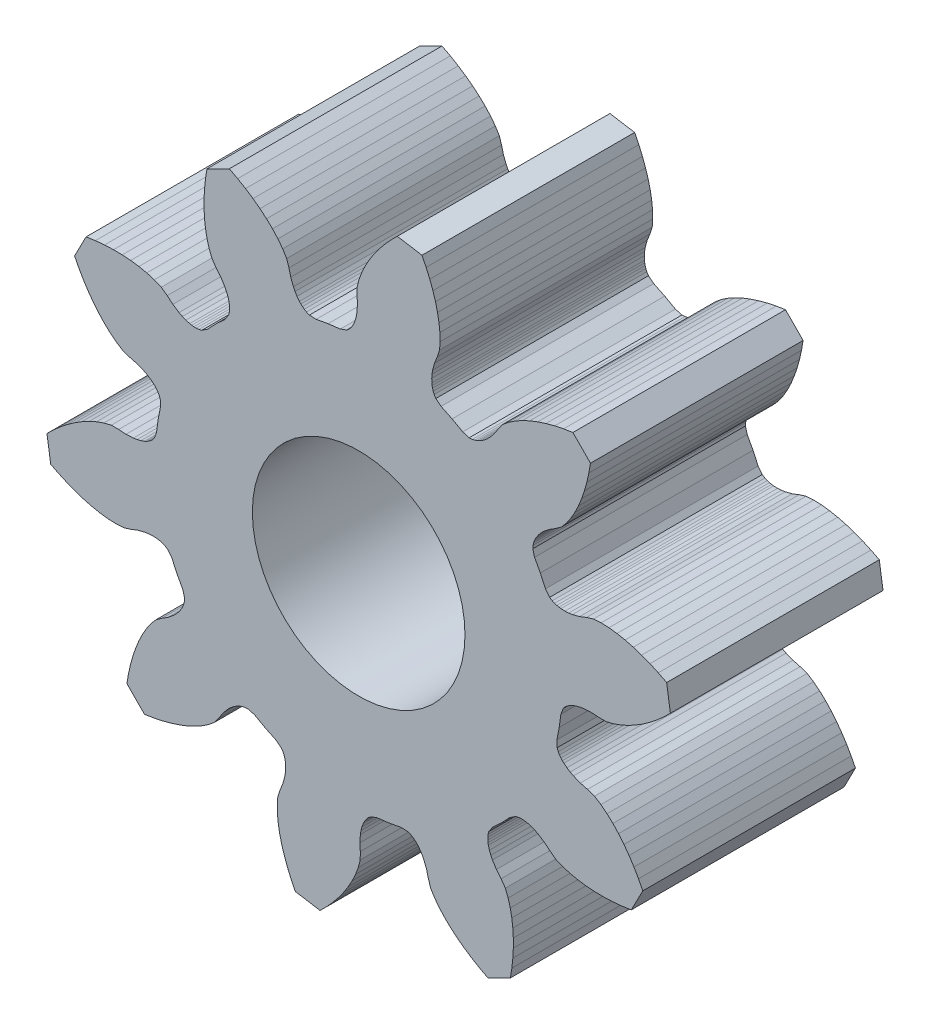
SolidWorks part; units mm, degrees
material "1060 Alloy"
ref_plane "Front Plane" through (0, 0, 0) normal (0, 0, 1) x (1, 0, 0)
ref_plane "Top Plane" through (0, 0, 0) normal (0, 1, 0) x (1, 0, 0)
ref_plane "Right Plane" through (0, 0, 0) normal (1, 0, 0) x (0, 0, -1)
sketch "Sketch1" plane through (0, 0, 0) normal (0, 0, 1) x (1, 0, 0)
  line L0 (-8.7858, -3.765) -> (-8.9815, -3.5156)
  line L1 (-8.9815, -3.5156) -> (-9.1044, -3.4371)
  line L2 (-9.1044, -3.4371) -> (-9.2148, -3.3885)
  line L3 (-9.2148, -3.3885) -> (-9.3186, -3.3562)
  line L4 (-9.3186, -3.3562) -> (-9.4181, -3.3349)
  line L5 (-9.4181, -3.3349) -> (-9.5145, -3.3217)
  line L6 (-9.5145, -3.3217) -> (-9.7003, -3.3138)
  line L7 (-9.7003, -3.3138) -> (-9.8793, -3.3247)
  line L8 (-9.8793, -3.3247) -> (-10.0533, -3.3502)
  line L9 (-10.0533, -3.3502) -> (-10.3894, -3.4364)
  line L10 (-10.3894, -3.4364) -> (-10.7128, -3.5607)
  line L11 (-10.7128, -3.5607) -> (-11.0431, -3.6644)
  line L12 (-11.0431, -3.6644) -> (-11.4, -3.6866)
  line L13 (-11.4, -3.6866) -> (-11.7679, -3.6716)
  line L14 (-11.7679, -3.6716) -> (-12.1438, -3.6256)
  line L15 (-12.1438, -3.6256) -> (-12.5259, -3.5514)
  line L16 (-12.5259, -3.5514) -> (-12.9126, -3.4504)
  line L17 (-12.9126, -3.4504) -> (-13.3028, -3.3238)
  line L18 (-13.3028, -3.3238) -> (-13.6953, -3.1723)
  line L19 (-13.6953, -3.1723) -> (-14.0889, -2.9962)
  line L20 (-14.0889, -2.9962) -> (-14.4827, -2.7961)
  line L21 (-14.4827, -2.7961) -> (-14.6595, -1.6321)
  line L22 (-14.6595, -1.6321) -> (-14.343, -1.324)
  line L23 (-14.343, -1.324) -> (-14.0194, -1.039)
  line L24 (-14.0194, -1.039) -> (-13.6897, -0.7777)
  line L25 (-13.6897, -0.7777) -> (-13.3547, -0.5409)
  line L26 (-13.3547, -0.5409) -> (-13.0154, -0.3297)
  line L27 (-13.0154, -0.3297) -> (-12.6726, -0.1453)
  line L28 (-12.6726, -0.1453) -> (-12.3273, 0.0103)
  line L29 (-12.3273, 0.0103) -> (-11.9805, 0.1339)
  line L30 (-11.9805, 0.1339) -> (-11.6331, 0.2187)
  line L31 (-11.6331, 0.2187) -> (-11.2869, 0.2178)
  line L32 (-11.2869, 0.2178) -> (-10.9412, 0.1951)
  line L33 (-10.9412, 0.1951) -> (-10.5947, 0.2127)
  line L34 (-10.5947, 0.2127) -> (-10.421, 0.24)
  line L35 (-10.421, 0.24) -> (-10.2468, 0.2828)
  line L36 (-10.2468, 0.2828) -> (-10.0717, 0.3455)
  line L37 (-10.0717, 0.3455) -> (-9.9836, 0.3867)
  line L38 (-9.9836, 0.3867) -> (-9.895, 0.4366)
  line L39 (-9.895, 0.4366) -> (-9.8054, 0.4983)
  line L40 (-9.8054, 0.4983) -> (-9.7144, 0.5775)
  line L41 (-9.7144, 0.5775) -> (-9.6204, 0.689)
  line L42 (-9.6204, 0.689) -> (-9.5076, 0.9853)
  line L43 (-9.5076, 0.9853) -> (-9.4312, 1.5547)
  line L44 (-9.4312, 1.5547) -> (-9.3208, 2.1184)
  line L45 (-9.3208, 2.1184) -> (-9.3325, 2.4352)
  line L46 (-9.3325, 2.4352) -> (-9.3858, 2.571)
  line L47 (-9.3858, 2.571) -> (-9.4466, 2.6752)
  line L48 (-9.4466, 2.6752) -> (-9.5116, 2.7624)
  line L49 (-9.5116, 2.7624) -> (-9.5796, 2.8381)
  line L50 (-9.5796, 2.8381) -> (-9.6498, 2.9054)
  line L51 (-9.6498, 2.9054) -> (-9.7955, 3.021)
  line L52 (-9.7955, 3.021) -> (-9.9467, 3.1175)
  line L53 (-9.9467, 3.1175) -> (-10.1024, 3.199)
  line L54 (-10.1024, 3.199) -> (-10.425, 3.3269)
  line L55 (-10.425, 3.3269) -> (-10.7597, 3.4164)
  line L56 (-10.7597, 3.4164) -> (-11.0878, 3.5266)
  line L57 (-11.0878, 3.5266) -> (-11.3896, 3.7184)
  line L58 (-11.3896, 3.7184) -> (-11.6785, 3.9468)
  line L59 (-11.6785, 3.9468) -> (-11.9556, 4.205)
  line L60 (-11.9556, 4.205) -> (-12.221, 4.4896)
  line L61 (-12.221, 4.4896) -> (-12.4746, 4.7986)
  line L62 (-12.4746, 4.7986) -> (-12.7159, 5.1304)
  line L63 (-12.7159, 5.1304) -> (-12.9443, 5.4837)
  line L64 (-12.9443, 5.4837) -> (-13.1593, 5.8575)
  line L65 (-13.1593, 5.8575) -> (-13.3602, 6.2508)
  line L66 (-13.3602, 6.2508) -> (-12.8191, 7.2965)
  line L67 (-12.8191, 7.2965) -> (-12.3819, 7.3597)
  line L68 (-12.3819, 7.3597) -> (-11.9526, 7.4001)
  line L69 (-11.9526, 7.4001) -> (-11.5323, 7.4176)
  line L70 (-11.5323, 7.4176) -> (-11.1221, 7.4123)
  line L71 (-11.1221, 7.4123) -> (-10.7234, 7.3838)
  line L72 (-10.7234, 7.3838) -> (-10.3377, 7.3315)
  line L73 (-10.3377, 7.3315) -> (-9.9669, 7.2544)
  line L74 (-9.9669, 7.2544) -> (-9.6137, 7.1505)
  line L75 (-9.6137, 7.1505) -> (-9.2828, 7.0149)
  line L76 (-9.2828, 7.0149) -> (-9.0033, 6.8107)
  line L77 (-9.0033, 6.8107) -> (-8.7368, 6.5892)
  line L78 (-8.7368, 6.5892) -> (-8.4462, 6.3997)
  line L79 (-8.4462, 6.3997) -> (-8.2897, 6.3197)
  line L80 (-8.2897, 6.3197) -> (-8.1236, 6.2519)
  line L81 (-8.1236, 6.2519) -> (-7.945, 6.1998)
  line L82 (-7.945, 6.1998) -> (-7.8496, 6.1813)
  line L83 (-7.8496, 6.1813) -> (-7.7485, 6.1696)
  line L84 (-7.7485, 6.1696) -> (-7.6398, 6.1668)
  line L85 (-7.6398, 6.1668) -> (-7.5196, 6.1774)
  line L86 (-7.5196, 6.1774) -> (-7.378, 6.2124)
  line L87 (-7.378, 6.2124) -> (-7.1126, 6.3858)
  line L88 (-7.1126, 6.3858) -> (-6.7162, 6.8015)
  line L89 (-6.7162, 6.8015) -> (-6.2955, 7.1927)
  line L90 (-6.2955, 7.1927) -> (-6.1188, 7.4559)
  line L91 (-6.1188, 7.4559) -> (-6.082, 7.597)
  line L92 (-6.082, 7.597) -> (-6.07, 7.7171)
  line L93 (-6.07, 7.7171) -> (-6.0713, 7.8258)
  line L94 (-6.0713, 7.8258) -> (-6.0818, 7.927)
  line L95 (-6.0818, 7.927) -> (-6.099, 8.0227)
  line L96 (-6.099, 8.0227) -> (-6.1489, 8.2019)
  line L97 (-6.1489, 8.2019) -> (-6.2146, 8.3688)
  line L98 (-6.2146, 8.3688) -> (-6.2927, 8.5263)
  line L99 (-6.2927, 8.5263) -> (-6.4784, 8.8194)
  line L100 (-6.4784, 8.8194) -> (-6.6966, 9.0885)
  line L101 (-6.6966, 9.0885) -> (-6.8973, 9.3706)
  line L102 (-6.8973, 9.3706) -> (-7.0287, 9.7032)
  line L103 (-7.0287, 9.7032) -> (-7.1282, 10.0577)
  line L104 (-7.1282, 10.0577) -> (-7.2006, 10.4294)
  line L105 (-7.2006, 10.4294) -> (-7.248, 10.8157)
  line L106 (-7.248, 10.8157) -> (-7.2715, 11.2148)
  line L107 (-7.2715, 11.2148) -> (-7.2717, 11.625)
  line L108 (-7.2717, 11.625) -> (-7.2489, 12.0451)
  line L109 (-7.2489, 12.0451) -> (-7.2031, 12.4739)
  line L110 (-7.2031, 12.4739) -> (-7.1344, 12.9102)
  line L111 (-7.1344, 12.9102) -> (-6.0821, 13.4381)
  line L112 (-6.0821, 13.4381) -> (-5.6913, 13.2322)
  line L113 (-5.6913, 13.2322) -> (-5.3202, 13.0126)
  line L114 (-5.3202, 13.0126) -> (-4.9698, 12.7797)
  line L115 (-4.9698, 12.7797) -> (-4.6411, 12.5343)
  line L116 (-4.6411, 12.5343) -> (-4.3353, 12.2769)
  line L117 (-4.3353, 12.2769) -> (-4.054, 12.0079)
  line L118 (-4.054, 12.0079) -> (-3.7993, 11.7276)
  line L119 (-3.7993, 11.7276) -> (-3.5746, 11.4359)
  line L120 (-3.5746, 11.4359) -> (-3.3866, 11.1317)
  line L121 (-3.3866, 11.1317) -> (-3.2805, 10.8022)
  line L122 (-3.2805, 10.8022) -> (-3.1952, 10.4664)
  line L123 (-3.1952, 10.4664) -> (-3.0714, 10.1422)
  line L124 (-3.0714, 10.1422) -> (-2.9918, 9.9855)
  line L125 (-2.9918, 9.9855) -> (-2.8973, 9.833)
  line L126 (-2.8973, 9.833) -> (-2.7835, 9.6859)
  line L127 (-2.7835, 9.6859) -> (-2.7171, 9.6149)
  line L128 (-2.7171, 9.6149) -> (-2.6422, 9.546)
  line L129 (-2.6422, 9.546) -> (-2.5559, 9.4799)
  line L130 (-2.5559, 9.4799) -> (-2.4524, 9.4178)
  line L131 (-2.4524, 9.4178) -> (-2.3173, 9.3628)
  line L132 (-2.3173, 9.3628) -> (-2.0007, 9.3471)
  line L133 (-2.0007, 9.3471) -> (-1.4356, 9.4504)
  line L134 (-1.4356, 9.4504) -> (-0.8654, 9.5196)
  line L135 (-0.8654, 9.5196) -> (-0.5677, 9.6287)
  line L136 (-0.5677, 9.6287) -> (-0.455, 9.7213)
  line L137 (-0.455, 9.7213) -> (-0.3747, 9.8113)
  line L138 (-0.3747, 9.8113) -> (-0.3119, 9.9001)
  line L139 (-0.3119, 9.9001) -> (-0.2608, 9.9881)
  line L140 (-0.2608, 9.9881) -> (-0.2185, 10.0757)
  line L141 (-0.2185, 10.0757) -> (-0.1536, 10.2499)
  line L142 (-0.1536, 10.2499) -> (-0.1086, 10.4236)
  line L143 (-0.1086, 10.4236) -> (-0.0792, 10.5969)
  line L144 (-0.0792, 10.5969) -> (-0.0572, 10.9432)
  line L145 (-0.0572, 10.9432) -> (-0.0755, 11.2892)
  line L146 (-0.0755, 11.2892) -> (-0.0721, 11.6353)
  line L147 (-0.0721, 11.6353) -> (0.0171, 11.9816)
  line L148 (0.0171, 11.9816) -> (0.145, 12.3269)
  line L149 (0.145, 12.3269) -> (0.3049, 12.6702)
  line L150 (0.3049, 12.6702) -> (0.4936, 13.0106)
  line L151 (0.4936, 13.0106) -> (0.7091, 13.3473)
  line L152 (0.7091, 13.3473) -> (0.9501, 13.6793)
  line L153 (0.9501, 13.6793) -> (1.2155, 14.0057)
  line L154 (1.2155, 14.0057) -> (1.5046, 14.3256)
  line L155 (1.5046, 14.3256) -> (1.8166, 14.6383)
  line L156 (1.8166, 14.6383) -> (2.9783, 14.4468)
  line L157 (2.9783, 14.4468) -> (3.1734, 14.0506)
  line L158 (3.1734, 14.0506) -> (3.3445, 13.6548)
  line L159 (3.3445, 13.6548) -> (3.4911, 13.2604)
  line L160 (3.4911, 13.2604) -> (3.6128, 12.8687)
  line L161 (3.6128, 12.8687) -> (3.7089, 12.4806)
  line L162 (3.7089, 12.4806) -> (3.7783, 12.0977)
  line L163 (3.7783, 12.0977) -> (3.8196, 11.7212)
  line L164 (3.8196, 11.7212) -> (3.83, 11.3531)
  line L165 (3.83, 11.3531) -> (3.8032, 10.9965)
  line L166 (3.8032, 10.9965) -> (3.6954, 10.6676)
  line L167 (3.6954, 10.6676) -> (3.567, 10.3458)
  line L168 (3.567, 10.3458) -> (3.4767, 10.0108)
  line L169 (3.4767, 10.0108) -> (3.4489, 9.8372)
  line L170 (3.4489, 9.8372) -> (3.4358, 9.6583)
  line L171 (3.4358, 9.6583) -> (3.4414, 9.4724)
  line L172 (3.4414, 9.4724) -> (3.4534, 9.3759)
  line L173 (3.4534, 9.3759) -> (3.4734, 9.2761)
  line L174 (3.4734, 9.2761) -> (3.5044, 9.1719)
  line L175 (3.5044, 9.1719) -> (3.5516, 9.0609)
  line L176 (3.5516, 9.0609) -> (3.6286, 8.937)
  line L177 (3.6286, 8.937) -> (3.8755, 8.7381)
  line L178 (3.8755, 8.7381) -> (4.3934, 8.4896)
  line L179 (4.3934, 8.4896) -> (4.8954, 8.2104)
  line L180 (4.8954, 8.2104) -> (5.2004, 8.1237)
  line L181 (5.2004, 8.1237) -> (5.346, 8.1323)
  line L182 (5.346, 8.1323) -> (5.4639, 8.1579)
  line L183 (5.4639, 8.1579) -> (5.5669, 8.1929)
  line L184 (5.5669, 8.1929) -> (5.6599, 8.2341)
  line L185 (5.6599, 8.2341) -> (5.7456, 8.2801)
  line L186 (5.7456, 8.2801) -> (5.9005, 8.3829)
  line L187 (5.9005, 8.3829) -> (6.039, 8.4969)
  line L188 (6.039, 8.4969) -> (6.1647, 8.6198)
  line L189 (6.1647, 8.6198) -> (6.386, 8.8871)
  line L190 (6.386, 8.8871) -> (6.5746, 9.1777)
  line L191 (6.5746, 9.1777) -> (6.7808, 9.4557)
  line L192 (6.7808, 9.4557) -> (7.0565, 9.6835)
  line L193 (7.0565, 9.6835) -> (7.3629, 9.8877)
  line L194 (7.3629, 9.8877) -> (7.6941, 10.0714)
  line L195 (7.6941, 10.0714) -> (8.0468, 10.2359)
  line L196 (8.0468, 10.2359) -> (8.4191, 10.3816)
  line L197 (8.4191, 10.3816) -> (8.8092, 10.5085)
  line L198 (8.8092, 10.5085) -> (9.2158, 10.6166)
  line L199 (9.2158, 10.6166) -> (9.6377, 10.7055)
  line L200 (9.6377, 10.7055) -> (10.0739, 10.7751)
  line L201 (10.0739, 10.7751) -> (10.9011, 9.9373)
  line L202 (10.9011, 9.9373) -> (10.8261, 9.5021)
  line L203 (10.8261, 9.5021) -> (10.7319, 9.0813)
  line L204 (10.7319, 9.0813) -> (10.6187, 8.6761)
  line L205 (10.6187, 8.6761) -> (10.4869, 8.2876)
  line L206 (10.4869, 8.2876) -> (10.3365, 7.9173)
  line L207 (10.3365, 7.9173) -> (10.1676, 7.5666)
  line L208 (10.1676, 7.5666) -> (9.9797, 7.2377)
  line L209 (9.9797, 7.2377) -> (9.7718, 6.9339)
  line L210 (9.7718, 6.9339) -> (9.5405, 6.6611)
  line L211 (9.5405, 6.6611) -> (9.26, 6.4584)
  line L212 (9.26, 6.4584) -> (8.9669, 6.2735)
  line L213 (8.9669, 6.2735) -> (8.6969, 6.0556)
  line L214 (8.6969, 6.0556) -> (8.5725, 5.9314)
  line L215 (8.5725, 5.9314) -> (8.4567, 5.7944)
  line L216 (8.4567, 5.7944) -> (8.3519, 5.6407)
  line L217 (8.3519, 5.6407) -> (8.3049, 5.5556)
  line L218 (8.3049, 5.5556) -> (8.2625, 5.4631)
  line L219 (8.2625, 5.4631) -> (8.2263, 5.3606)
  line L220 (8.2263, 5.3606) -> (8.1992, 5.243)
  line L221 (8.1992, 5.243) -> (8.1887, 5.0975)
  line L222 (8.1887, 5.0975) -> (8.2716, 4.7916)
  line L223 (8.2716, 4.7916) -> (8.5445, 4.2861)
  line L224 (8.5445, 4.2861) -> (8.7865, 3.7651)
  line L225 (8.7865, 3.7651) -> (8.9822, 3.5157)
  line L226 (8.9822, 3.5157) -> (9.1051, 3.4371)
  line L227 (9.1051, 3.4371) -> (9.2155, 3.3885)
  line L228 (9.2155, 3.3885) -> (9.3194, 3.3563)
  line L229 (9.3194, 3.3563) -> (9.4189, 3.3349)
  line L230 (9.4189, 3.3349) -> (9.5152, 3.3218)
  line L231 (9.5152, 3.3218) -> (9.701, 3.3139)
  line L232 (9.701, 3.3139) -> (9.8801, 3.3247)
  line L233 (9.8801, 3.3247) -> (10.054, 3.3503)
  line L234 (10.054, 3.3503) -> (10.3901, 3.4364)
  line L235 (10.3901, 3.4364) -> (10.7135, 3.5607)
  line L236 (10.7135, 3.5607) -> (11.0438, 3.6644)
  line L237 (11.0438, 3.6644) -> (11.4007, 3.6867)
  line L238 (11.4007, 3.6867) -> (11.7686, 3.6717)
  line L239 (11.7686, 3.6717) -> (12.1445, 3.6257)
  line L240 (12.1445, 3.6257) -> (12.5266, 3.5514)
  line L241 (12.5266, 3.5514) -> (12.9134, 3.4505)
  line L242 (12.9134, 3.4505) -> (13.3036, 3.3239)
  line L243 (13.3036, 3.3239) -> (13.696, 3.1723)
  line L244 (13.696, 3.1723) -> (14.0897, 2.9963)
  line L245 (14.0897, 2.9963) -> (14.4834, 2.7962)
  line L246 (14.4834, 2.7962) -> (14.6603, 1.6322)
  line L247 (14.6603, 1.6322) -> (14.3438, 1.3241)
  line L248 (14.3438, 1.3241) -> (14.0202, 1.0391)
  line L249 (14.0202, 1.0391) -> (13.6904, 0.7778)
  line L250 (13.6904, 0.7778) -> (13.3555, 0.541)
  line L251 (13.3555, 0.541) -> (13.0161, 0.3297)
  line L252 (13.0161, 0.3297) -> (12.6734, 0.1453)
  line L253 (12.6734, 0.1453) -> (12.3281, -0.0103)
  line L254 (12.3281, -0.0103) -> (11.9812, -0.1338)
  line L255 (11.9812, -0.1338) -> (11.6338, -0.2186)
  line L256 (11.6338, -0.2186) -> (11.2877, -0.2177)
  line L257 (11.2877, -0.2177) -> (10.9419, -0.1951)
  line L258 (10.9419, -0.1951) -> (10.5954, -0.2126)
  line L259 (10.5954, -0.2126) -> (10.4217, -0.2399)
  line L260 (10.4217, -0.2399) -> (10.2475, -0.2827)
  line L261 (10.2475, -0.2827) -> (10.0725, -0.3455)
  line L262 (10.0725, -0.3455) -> (9.9844, -0.3867)
  line L263 (9.9844, -0.3867) -> (9.8957, -0.4366)
  line L264 (9.8957, -0.4366) -> (9.8061, -0.4982)
  line L265 (9.8061, -0.4982) -> (9.7151, -0.5774)
  line L266 (9.7151, -0.5774) -> (9.6211, -0.689)
  line L267 (9.6211, -0.689) -> (9.5083, -0.9852)
  line L268 (9.5083, -0.9852) -> (9.4319, -1.5546)
  line L269 (9.4319, -1.5546) -> (9.3215, -2.1183)
  line L270 (9.3215, -2.1183) -> (9.3333, -2.4351)
  line L271 (9.3333, -2.4351) -> (9.3865, -2.5709)
  line L272 (9.3865, -2.5709) -> (9.4473, -2.6751)
  line L273 (9.4473, -2.6751) -> (9.5123, -2.7623)
  line L274 (9.5123, -2.7623) -> (9.5803, -2.838)
  line L275 (9.5803, -2.838) -> (9.6505, -2.9053)
  line L276 (9.6505, -2.9053) -> (9.7962, -3.0209)
  line L277 (9.7962, -3.0209) -> (9.9474, -3.1174)
  line L278 (9.9474, -3.1174) -> (10.1032, -3.199)
  line L279 (10.1032, -3.199) -> (10.4257, -3.3268)
  line L280 (10.4257, -3.3268) -> (10.7604, -3.4163)
  line L281 (10.7604, -3.4163) -> (11.0886, -3.5266)
  line L282 (11.0886, -3.5266) -> (11.3904, -3.7184)
  line L283 (11.3904, -3.7184) -> (11.6792, -3.9467)
  line L284 (11.6792, -3.9467) -> (11.9563, -4.2049)
  line L285 (11.9563, -4.2049) -> (12.2217, -4.4896)
  line L286 (12.2217, -4.4896) -> (12.4753, -4.7986)
  line L287 (12.4753, -4.7986) -> (12.7166, -5.1303)
  line L288 (12.7166, -5.1303) -> (12.945, -5.4836)
  line L289 (12.945, -5.4836) -> (13.16, -5.8574)
  line L290 (13.16, -5.8574) -> (13.3609, -6.2508)
  line L291 (13.3609, -6.2508) -> (12.8198, -7.2964)
  line L292 (12.8198, -7.2964) -> (12.3827, -7.3596)
  line L293 (12.3827, -7.3596) -> (11.9534, -7.4)
  line L294 (11.9534, -7.4) -> (11.533, -7.4176)
  line L295 (11.533, -7.4176) -> (11.1228, -7.4122)
  line L296 (11.1228, -7.4122) -> (10.7241, -7.3837)
  line L297 (10.7241, -7.3837) -> (10.3384, -7.3314)
  line L298 (10.3384, -7.3314) -> (9.9676, -7.2543)
  line L299 (9.9676, -7.2543) -> (9.6144, -7.1504)
  line L300 (9.6144, -7.1504) -> (9.2835, -7.0148)
  line L301 (9.2835, -7.0148) -> (9.004, -6.8106)
  line L302 (9.004, -6.8106) -> (8.7376, -6.5891)
  line L303 (8.7376, -6.5891) -> (8.4469, -6.3996)
  line L304 (8.4469, -6.3996) -> (8.2904, -6.3196)
  line L305 (8.2904, -6.3196) -> (8.1243, -6.2519)
  line L306 (8.1243, -6.2519) -> (7.9458, -6.1997)
  line L307 (7.9458, -6.1997) -> (7.8503, -6.1812)
  line L308 (7.8503, -6.1812) -> (7.7492, -6.1695)
  line L309 (7.7492, -6.1695) -> (7.6405, -6.1668)
  line L310 (7.6405, -6.1668) -> (7.5203, -6.1773)
  line L311 (7.5203, -6.1773) -> (7.3787, -6.2123)
  line L312 (7.3787, -6.2123) -> (7.1133, -6.3857)
  line L313 (7.1133, -6.3857) -> (6.7169, -6.8014)
  line L314 (6.7169, -6.8014) -> (6.2962, -7.1926)
  line L315 (6.2962, -7.1926) -> (6.1195, -7.4558)
  line L316 (6.1195, -7.4558) -> (6.0828, -7.597)
  line L317 (6.0828, -7.597) -> (6.0707, -7.717)
  line L318 (6.0707, -7.717) -> (6.0721, -7.8257)
  line L319 (6.0721, -7.8257) -> (6.0825, -7.927)
  line L320 (6.0825, -7.927) -> (6.0998, -8.0227)
  line L321 (6.0998, -8.0227) -> (6.1497, -8.2018)
  line L322 (6.1497, -8.2018) -> (6.2153, -8.3687)
  line L323 (6.2153, -8.3687) -> (6.2934, -8.5263)
  line L324 (6.2934, -8.5263) -> (6.4792, -8.8193)
  line L325 (6.4792, -8.8193) -> (6.6973, -9.0885)
  line L326 (6.6973, -9.0885) -> (6.898, -9.3705)
  line L327 (6.898, -9.3705) -> (7.0294, -9.7031)
  line L328 (7.0294, -9.7031) -> (7.1289, -10.0576)
  line L329 (7.1289, -10.0576) -> (7.2013, -10.4293)
  line L330 (7.2013, -10.4293) -> (7.2488, -10.8157)
  line L331 (7.2488, -10.8157) -> (7.2723, -11.2147)
  line L332 (7.2723, -11.2147) -> (7.2725, -11.6249)
  line L333 (7.2725, -11.6249) -> (7.2496, -12.045)
  line L334 (7.2496, -12.045) -> (7.2038, -12.4738)
  line L335 (7.2038, -12.4738) -> (7.1351, -12.9101)
  line L336 (7.1351, -12.9101) -> (6.0828, -13.438)
  line L337 (6.0828, -13.438) -> (5.692, -13.2322)
  line L338 (5.692, -13.2322) -> (5.3209, -13.0125)
  line L339 (5.3209, -13.0125) -> (4.9705, -12.7797)
  line L340 (4.9705, -12.7797) -> (4.6418, -12.5342)
  line L341 (4.6418, -12.5342) -> (4.336, -12.2768)
  line L342 (4.336, -12.2768) -> (4.0547, -12.0078)
  line L343 (4.0547, -12.0078) -> (3.8, -11.7275)
  line L344 (3.8, -11.7275) -> (3.5754, -11.4358)
  line L345 (3.5754, -11.4358) -> (3.3874, -11.1316)
  line L346 (3.3874, -11.1316) -> (3.2812, -10.8021)
  line L347 (3.2812, -10.8021) -> (3.1959, -10.4663)
  line L348 (3.1959, -10.4663) -> (3.0722, -10.1422)
  line L349 (3.0722, -10.1422) -> (2.9925, -9.9854)
  line L350 (2.9925, -9.9854) -> (2.898, -9.833)
  line L351 (2.898, -9.833) -> (2.7842, -9.6859)
  line L352 (2.7842, -9.6859) -> (2.7178, -9.6148)
  line L353 (2.7178, -9.6148) -> (2.6429, -9.5459)
  line L354 (2.6429, -9.5459) -> (2.5566, -9.4798)
  line L355 (2.5566, -9.4798) -> (2.4532, -9.4177)
  line L356 (2.4532, -9.4177) -> (2.3181, -9.3627)
  line L357 (2.3181, -9.3627) -> (2.0014, -9.347)
  line L358 (2.0014, -9.347) -> (1.4363, -9.4503)
  line L359 (1.4363, -9.4503) -> (0.8661, -9.5195)
  line L360 (0.8661, -9.5195) -> (0.5684, -9.6286)
  line L361 (0.5684, -9.6286) -> (0.4557, -9.7212)
  line L362 (0.4557, -9.7212) -> (0.3754, -9.8112)
  line L363 (0.3754, -9.8112) -> (0.3126, -9.9)
  line L364 (0.3126, -9.9) -> (0.2616, -9.988)
  line L365 (0.2616, -9.988) -> (0.2193, -10.0756)
  line L366 (0.2193, -10.0756) -> (0.1543, -10.2499)
  line L367 (0.1543, -10.2499) -> (0.1093, -10.4235)
  line L368 (0.1093, -10.4235) -> (0.0799, -10.5968)
  line L369 (0.0799, -10.5968) -> (0.058, -10.9431)
  line L370 (0.058, -10.9431) -> (0.0762, -11.2891)
  line L371 (0.0762, -11.2891) -> (0.0728, -11.6352)
  line L372 (0.0728, -11.6352) -> (-0.0163, -11.9816)
  line L373 (-0.0163, -11.9816) -> (-0.1442, -12.3268)
  line L374 (-0.1442, -12.3268) -> (-0.3042, -12.6701)
  line L375 (-0.3042, -12.6701) -> (-0.4929, -13.0106)
  line L376 (-0.4929, -13.0106) -> (-0.7084, -13.3472)
  line L377 (-0.7084, -13.3472) -> (-0.9494, -13.6792)
  line L378 (-0.9494, -13.6792) -> (-1.2148, -14.0056)
  line L379 (-1.2148, -14.0056) -> (-1.5038, -14.3256)
  line L380 (-1.5038, -14.3256) -> (-1.8159, -14.6382)
  line L381 (-1.8159, -14.6382) -> (-2.9775, -14.4467)
  line L382 (-2.9775, -14.4467) -> (-3.1727, -14.0505)
  line L383 (-3.1727, -14.0505) -> (-3.3438, -13.6547)
  line L384 (-3.3438, -13.6547) -> (-3.4904, -13.2603)
  line L385 (-3.4904, -13.2603) -> (-3.6121, -12.8686)
  line L386 (-3.6121, -12.8686) -> (-3.7081, -12.4806)
  line L387 (-3.7081, -12.4806) -> (-3.7776, -12.0976)
  line L388 (-3.7776, -12.0976) -> (-3.8189, -11.7211)
  line L389 (-3.8189, -11.7211) -> (-3.8292, -11.3531)
  line L390 (-3.8292, -11.3531) -> (-3.8025, -10.9965)
  line L391 (-3.8025, -10.9965) -> (-3.6947, -10.6675)
  line L392 (-3.6947, -10.6675) -> (-3.5663, -10.3457)
  line L393 (-3.5663, -10.3457) -> (-3.4759, -10.0107)
  line L394 (-3.4759, -10.0107) -> (-3.4482, -9.8371)
  line L395 (-3.4482, -9.8371) -> (-3.4351, -9.6582)
  line L396 (-3.4351, -9.6582) -> (-3.4407, -9.4723)
  line L397 (-3.4407, -9.4723) -> (-3.4526, -9.3758)
  line L398 (-3.4526, -9.3758) -> (-3.4727, -9.2761)
  line L399 (-3.4727, -9.2761) -> (-3.5037, -9.1718)
  line L400 (-3.5037, -9.1718) -> (-3.5509, -9.0608)
  line L401 (-3.5509, -9.0608) -> (-3.6279, -8.9369)
  line L402 (-3.6279, -8.9369) -> (-3.8748, -8.7381)
  line L403 (-3.8748, -8.7381) -> (-4.3927, -8.4895)
  line L404 (-4.3927, -8.4895) -> (-4.8947, -8.2103)
  line L405 (-4.8947, -8.2103) -> (-5.1996, -8.1236)
  line L406 (-5.1996, -8.1236) -> (-5.3452, -8.1323)
  line L407 (-5.3452, -8.1323) -> (-5.4632, -8.1579)
  line L408 (-5.4632, -8.1579) -> (-5.5661, -8.1928)
  line L409 (-5.5661, -8.1928) -> (-5.6592, -8.234)
  line L410 (-5.6592, -8.234) -> (-5.7448, -8.28)
  line L411 (-5.7448, -8.28) -> (-5.8998, -8.3828)
  line L412 (-5.8998, -8.3828) -> (-6.0383, -8.4968)
  line L413 (-6.0383, -8.4968) -> (-6.164, -8.6198)
  line L414 (-6.164, -8.6198) -> (-6.3852, -8.887)
  line L415 (-6.3852, -8.887) -> (-6.5738, -9.1777)
  line L416 (-6.5738, -9.1777) -> (-6.7801, -9.4557)
  line L417 (-6.7801, -9.4557) -> (-7.0558, -9.6835)
  line L418 (-7.0558, -9.6835) -> (-7.3622, -9.8876)
  line L419 (-7.3622, -9.8876) -> (-7.6933, -10.0713)
  line L420 (-7.6933, -10.0713) -> (-8.0461, -10.2358)
  line L421 (-8.0461, -10.2358) -> (-8.4183, -10.3815)
  line L422 (-8.4183, -10.3815) -> (-8.8084, -10.5085)
  line L423 (-8.8084, -10.5085) -> (-9.215, -10.6165)
  line L424 (-9.215, -10.6165) -> (-9.637, -10.7055)
  line L425 (-9.637, -10.7055) -> (-10.0731, -10.775)
  line L426 (-10.0731, -10.775) -> (-10.9004, -9.9373)
  line L427 (-10.9004, -9.9373) -> (-10.8254, -9.502)
  line L428 (-10.8254, -9.502) -> (-10.7312, -9.0812)
  line L429 (-10.7312, -9.0812) -> (-10.618, -8.676)
  line L430 (-10.618, -8.676) -> (-10.4862, -8.2876)
  line L431 (-10.4862, -8.2876) -> (-10.3358, -7.9172)
  line L432 (-10.3358, -7.9172) -> (-10.1669, -7.5665)
  line L433 (-10.1669, -7.5665) -> (-9.979, -7.2377)
  line L434 (-9.979, -7.2377) -> (-9.771, -6.9339)
  line L435 (-9.771, -6.9339) -> (-9.5398, -6.661)
  line L436 (-9.5398, -6.661) -> (-9.2592, -6.4583)
  line L437 (-9.2592, -6.4583) -> (-8.9662, -6.2734)
  line L438 (-8.9662, -6.2734) -> (-8.6962, -6.0555)
  line L439 (-8.6962, -6.0555) -> (-8.5717, -5.9314)
  line L440 (-8.5717, -5.9314) -> (-8.456, -5.7943)
  line L441 (-8.456, -5.7943) -> (-8.3512, -5.6407)
  line L442 (-8.3512, -5.6407) -> (-8.3041, -5.5556)
  line L443 (-8.3041, -5.5556) -> (-8.2618, -5.4631)
  line L444 (-8.2618, -5.4631) -> (-8.2256, -5.3605)
  line L445 (-8.2256, -5.3605) -> (-8.1985, -5.243)
  line L446 (-8.1985, -5.243) -> (-8.188, -5.0975)
  line L447 (-8.188, -5.0975) -> (-8.2708, -4.7915)
  line L448 (-8.2708, -4.7915) -> (-8.5437, -4.286)
  line L449 (-8.5437, -4.286) -> (-8.7858, -3.765)
extrude "Extrude gear face" add sketch "Sketch1" along normal blind 10
sketch "Sketch3" plane through (0, 0, 0) normal (0, 0, -1) x (-1, 0, 0)
  circle A0 centre (0, 0) radius 5
  dimension "D1" = 10
extrude "Cut-Extrude1" cut sketch "Sketch3" against normal through all
